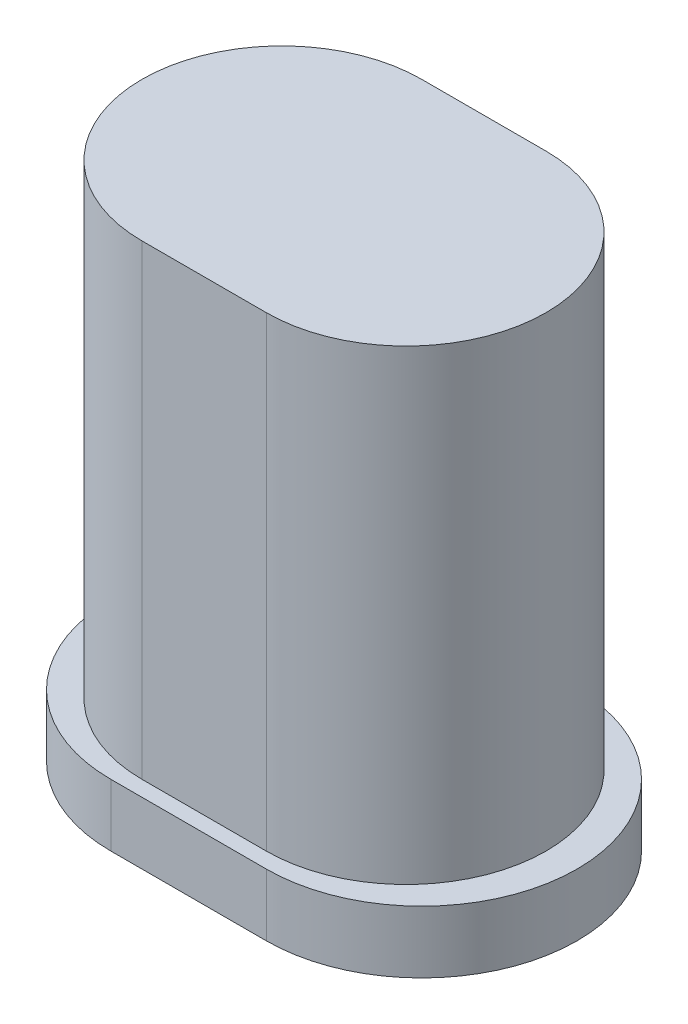
SolidWorks part; units mm, degrees
ref_plane "Front Plane" through (0, 0, 0) normal (0, 0, 1) x (1, 0, 0)
ref_plane "Top Plane" through (0, 0, 0) normal (0, 1, 0) x (1, 0, 0)
ref_plane "Right Plane" through (0, 0, 0) normal (1, 0, 0) x (0, 0, -1)
sketch "Sketch1" plane through (0, 0, 0) normal (0, 1, 0) x (1, 0, 0)
  line L0 (-1.25, 0) -> (1.25, 0) construction
  line L1 (-1.25, 2.5) -> (1.25, 2.5)
  line L2 (-1.25, -2.5) -> (1.25, -2.5)
  line L3 (-1.25, 0) -> (-3.75, 0) construction
  line L4 (1.25, 0) -> (3.75, 0) construction
  arc A0 (-1.25, 2.5) -> (-1.25, -2.5) centre (-1.25, 0) ccw
  arc A1 (1.25, -2.5) -> (1.25, 2.5) centre (1.25, 0) ccw
  point P2 (0, 0)
  dimension "D1" = 5
  dimension "D2" = 7.5
extrude "Boss-Extrude1" add sketch "Sketch1" along normal blind 1
sketch "Sketch2" plane through (0, 1, 0) normal (0, 1, 0) x (1, 0, 0)
  line L0 (-1, 0) -> (1, 0) construction
  line L1 (-1, 2.25) -> (1, 2.25)
  line L2 (-1, -2.25) -> (1, -2.25)
  arc A0 (-1, 2.25) -> (-1, -2.25) centre (-1, 0) ccw
  arc A1 (1, -2.25) -> (1, 2.25) centre (1, 0) ccw
  point P3 (0, 0)
  point P8 (-3.25, 0)
  point P9 (3.25, 0)
  dimension "D1" = 6.5
  dimension "D2" = 4.5
extrude "Boss-Extrude2" add sketch "Sketch2" along normal blind 7.5
